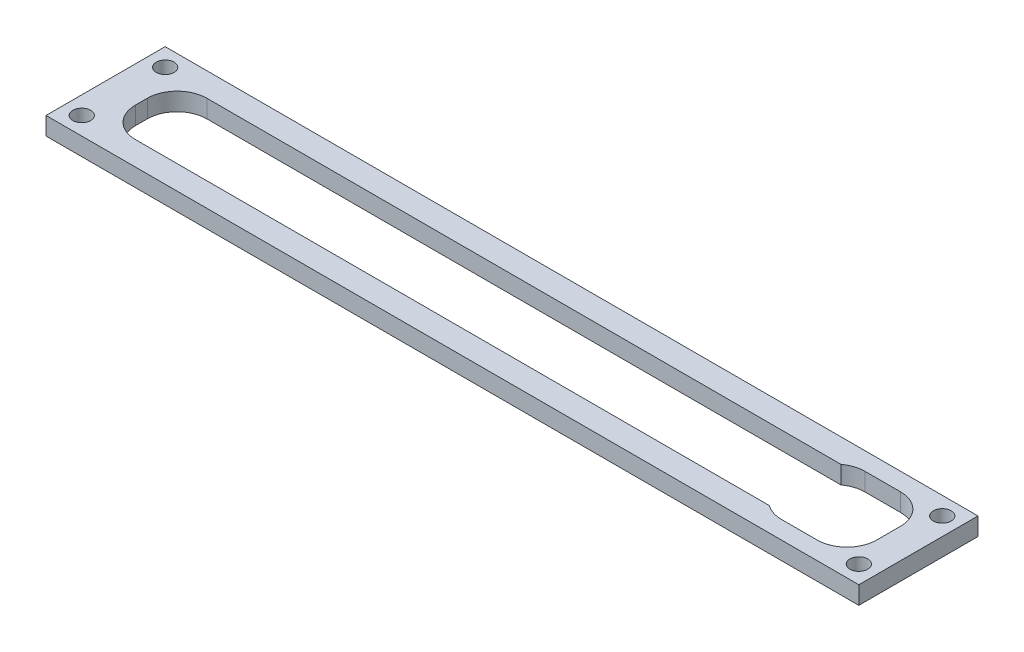
SolidWorks part; units mm, degrees
ref_plane "Front Plane" through (0, 0, 0) normal (0, 0, 1) x (1, 0, 0)
ref_plane "Top Plane" through (0, 0, 0) normal (0, 1, 0) x (1, 0, 0)
ref_plane "Right Plane" through (0, 0, 0) normal (1, 0, 0) x (0, 0, -1)
sketch "Sketch1" plane through (0, 0, 0) normal (0, 1, 0) x (1, 0, 0)
  line L0 (68.2139, 20) -> (68.2139, 0) construction
  line L1 (0, 0) -> (136.4278, 0)
  line L2 (0, 0) -> (0, 20)
  line L3 (0, 20) -> (136.4278, 20)
  line L4 (136.4278, 0) -> (136.4278, 20)
  line L5 (0, 10) -> (136.4278, 10) construction
  line L6 (68.2139, 16) -> (68.2139, 4) construction
  line L7 (6, 16) -> (130.4278, 16)
  line L8 (6, 16) -> (6, 4)
  line L9 (6, 4) -> (130.4278, 4)
  line L10 (130.4278, 16) -> (130.4278, 4)
  line L11 (6, 10) -> (130.4278, 10) construction
  circle A0 centre (3, 17) radius 1.5
  circle A1 centre (3, 3) radius 1.5
  circle A2 centre (133.4278, 3) radius 1.5
  circle A3 centre (133.4278, 17) radius 1.5
  point P17 (68.2139, 10)
  point P18 (68.2139, 10)
  dimension "D7" = 3
  dimension "D1" = 136.4278
  dimension "D2" = 20
  dimension "D3" = 124.4278
  dimension "D4" = 12
  dimension "D5" = 3
  dimension "D6" = 3
extrude "Boss-Extrude1" add sketch "Sketch1" along normal blind 3
sketch "Sketch2" plane through (0, 3, 0) normal (0, 1, 0) x (1, 0, 0)
  line L0 (92, 10) -> (-49908, 10) construction
  line L1 (130.4278, 4) -> (130.4278, 16) construction
  line L2 (117.4278, 17) -> (117.4278, 16)
  line L5 (130.4278, 16) -> (6, 16) construction
  line L6 (124.4278, 17) -> (124.4278, 3) construction
  line L7 (117.4278, 17) -> (131.4278, 17)
  line L9 (117.4278, 3) -> (131.4278, 3)
  line L10 (131.4278, 17) -> (131.4278, 3)
  line L12 (117.4278, 16) -> (130.4278, 16)
  line L13 (130.4278, 16) -> (130.4278, 4)
  line L14 (130.4278, 4) -> (117.4278, 4)
  line L15 (6, 4) -> (130.4278, 4) construction
  line L16 (117.4278, 4) -> (117.4278, 3)
  point P4 (130.4278, 10)
  point P23 (124.4278, 10)
  dimension "D1" = 1
  dimension "D2" = 14
  dimension "D3" = 14
extrude "Cut-Extrude1" cut sketch "Sketch2" against normal through all
fillet "Fillet1" radius 5 6 edges at (131.4278, 1.5, -17) (131.4278, 1.5, -3) (117.4278, 1.5, -17) (117.4278, 1.5, -3) (6, 1.5, -4) (6, 1.5, -16)
equation "\"TrackLength\"= ( ( \"n\" * 28 ) ) / cos ( \"MountAngle\" ) - ( 2 * \"x\" )"
equation "\"D1@Sketch1\"=\"TrackLength\""
equation "\"TrackWidth\"= \"MarbleTrackWidth\" + ( 2 * 4 )"
equation "\"D2@Sketch1\"=\"TrackWidth\""
equation "\"MarbleTrackWidth\"= \"MarbleWidth\" - 1"
equation "\"MarbleTrackLength\"= \"TrackLength\" - ( 2 * 6 )"
equation "\"D3@Sketch1\"=\"MarbleTrackLength\""
equation "\"D4@Sketch1\"=\"MarbleTrackWidth\""
equation "\"MarbleWidth\"= 13"
equation "\"n\"= 5"
equation "\"MountAngle\"= 5"
equation "\"x\"= 14 / cos ( \"MountAngle\" ) - 12"
